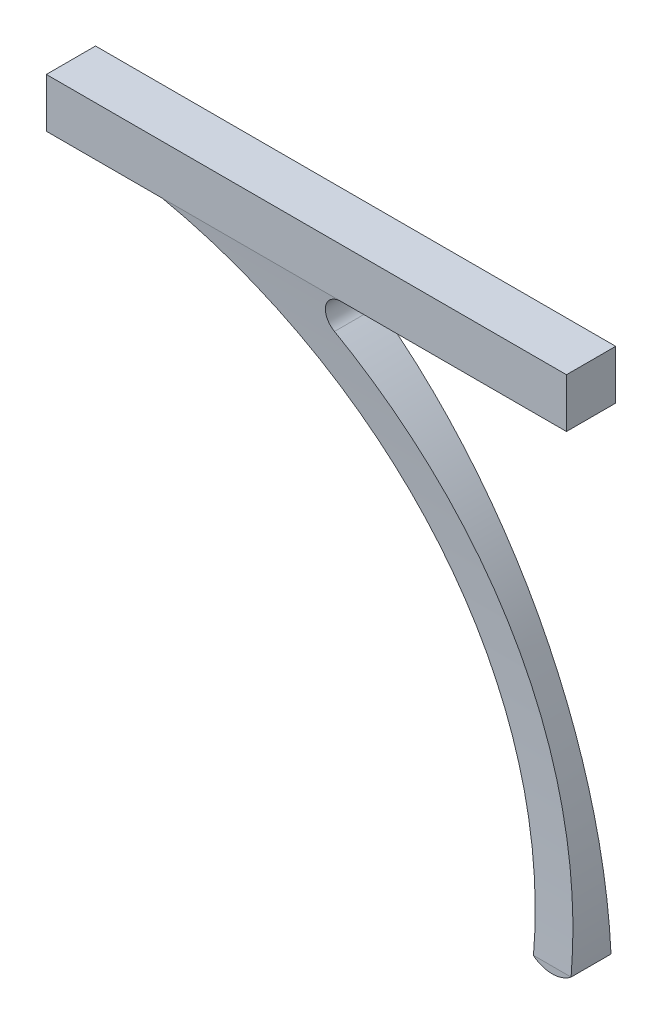
SolidWorks part; units mm, degrees
ref_plane "Plan de face" through (0, 0, 0) normal (0, 0, 1) x (1, 0, 0)
ref_plane "Plan de dessus" through (0, 0, 0) normal (0, 1, 0) x (1, 0, 0)
ref_plane "Plan de droite" through (0, 0, 0) normal (1, 0, 0) x (0, 0, -1)
sketch "Esquisse1" plane through (0, 0, 0) normal (0, 0, 1) x (1, 0, 0)
  line L0 (-224.5857, 132.2592) -> (-314.4196, 132.2592)
  line L1 (-314.4196, 132.2592) -> (-314.4196, 123.7592)
  line L2 (-294.4196, 123.7592) -> (-314.4196, 123.7592)
  line L3 (-274.971, 123.7592) -> (-224.5857, 123.7592)
  line L4 (-224.5857, 123.7592) -> (-224.5857, 132.2592)
  arc A0 (-231.0884, 41.7205) -> (-294.4196, 123.7592) centre (-313.2493, 43.7592) ccw
  arc A1 (-224.5857, 41.7576) -> (-274.971, 123.7592) centre (-313.2493, 43.7592) ccw
  arc A2 (-224.5857, 41.7576) -> (-231.0884, 41.7205) centre (-227.8602, 45.7986) cw
  dimension "D1" = 8.5
  dimension "D4" = 6.5
  dimension "D2" = 80
  dimension "D3" = 20
extrude "Boss.-Extru.1" add sketch "Esquisse1" along normal blind 8.5
fillet "Congé1" radius 3 1 edges at (-274.971, 123.7592, 4.25)
sketch "Esquisse2" plane through (-224.5857, 0, 0) normal (1, 0, 0) x (0, 0, -1)
  line L0 (-8.5, 41.7576) -> (0, 41.7576) construction
  line L1 (-4.25, 132.2592) -> (-4.25, 123.7592) construction
  line L2 (-8.5, 132.2592) -> (0, 132.2592) construction
  line L3 (-8.5, 123.7592) -> (0, 123.7592) construction
  line L6 (-8.5, 81.0544) -> (-8.5, 123.7592)
  line L7 (0, 123.7592) -> (0, 81.0544)
  line L9 (-0.8034, 41.7576) -> (-0.8034, 36.7726)
  line L10 (-0.8034, 36.7726) -> (0, 36.7726)
  line L11 (0, 36.7726) -> (0, 81.0544)
  line L12 (-7.6966, 41.7576) -> (-7.6966, 34.6411)
  line L13 (-7.6966, 34.6411) -> (-8.5, 34.6411)
  line L14 (-8.5, 34.6411) -> (-8.5, 81.0544)
  spline S0 degree 2 poles (-0.8034, 41.7576) (-3.625, 82.8445) (0, 123.7592) knots 0 0 0 1 1 1
  spline S1 degree 2 poles (-7.6966, 41.7576) (-4.875, 82.8445) (-8.5, 123.7592) knots 0 0 0 1 1 1
extrude "Enlèv. mat.-Extru.1" cut sketch "Esquisse2" against normal blind 75 and the other way blind 75
